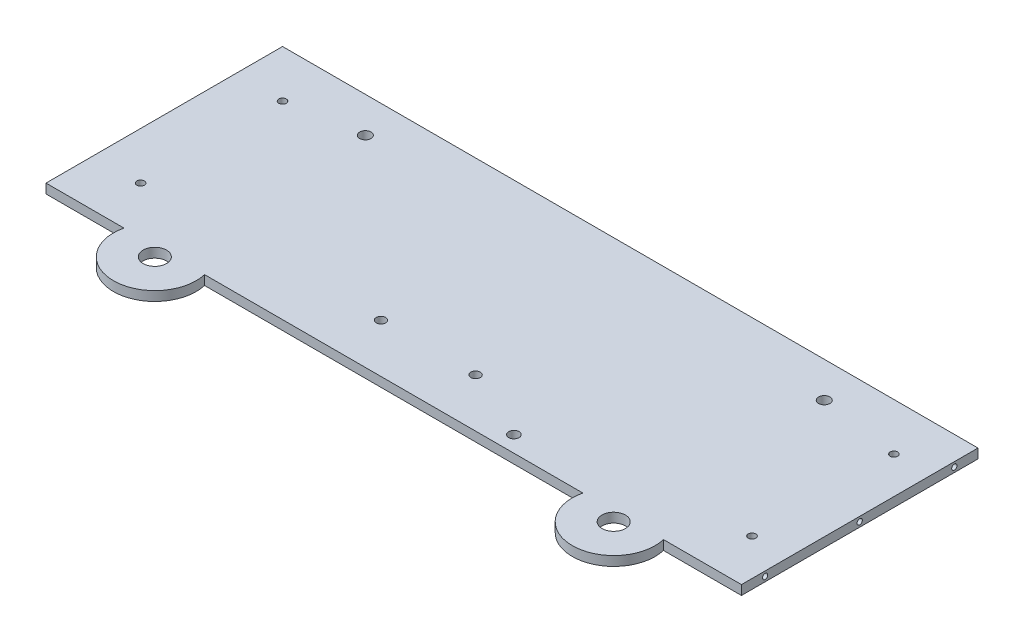
SolidWorks part; units mm, degrees
ref_plane "Front Plane" through (0, 0, 0) normal (0, 0, 1) x (1, 0, 0)
ref_plane "Top Plane" through (0, 0, 0) normal (0, 1, 0) x (1, 0, 0)
ref_plane "Right Plane" through (0, 0, 0) normal (1, 0, 0) x (0, 0, -1)
sketch "Sketch1" plane through (0, 0, 0) normal (0, 1, 0) x (1, 0, 0)
  line L0 (0, 0) -> (0, -63.5) construction
  line L1 (-186.69, -63.5) -> (186.69, -63.5)
  line L2 (-186.69, -63.5) -> (-186.69, 63.5)
  line L3 (-186.69, 63.5) -> (186.69, 63.5)
  line L4 (186.69, -63.5) -> (186.69, 63.5)
  line L5 (-186.69, -63.5) -> (186.69, 63.5) construction
  line L6 (-186.69, 63.5) -> (186.69, -63.5) construction
  line L7 (-123.19, -68.58) -> (-123.19, -63.5) construction
  line L8 (123.19, -68.58) -> (123.19, -63.5) construction
  line L9 (17.78, -37.338) -> (17.78, -63.5) construction
  circle A0 centre (-123.19, -68.58) radius 22.225
  circle A1 centre (123.19, -68.58) radius 22.225
  circle A2 centre (-123.19, -68.58) radius 6.2865
  circle A3 centre (123.19, -68.58) radius 6.2865
  circle A4 centre (-123.19, 44.45) radius 3.048
  circle A5 centre (123.19, 44.45) radius 3.048
  circle A6 centre (-33.02, -37.338) radius 2.54
  circle A7 centre (17.78, -37.338) radius 2.54
  circle A8 centre (0, -54.864) radius 3.175
  point P0 (0, 0)
  point P17 (123.19, 44.45)
  point P21 (-123.19, 44.45)
  dimension "D3" = 44.45
  dimension "D4" = 44.45
  dimension "D8" = 12.573
  dimension "D9" = 12.573
  dimension "D11" = 6.096
  dimension "D12" = 6.096
  dimension "D16" = 5.08
  dimension "D17" = 5.08
  dimension "D20" = 6.35
  dimension "D1" = 373.38
  dimension "D2" = 127
  dimension "D5" = 5.08
  dimension "D6" = 123.19
  dimension "D7" = 123.19
  dimension "D10" = 107.95
  dimension "D13" = 26.162
  dimension "D15" = 50.8
  dimension "D18" = 8.636
  dimension "D19" = 17.78
extrude "Boss-Extrude1" add sketch "Sketch1" along normal blind 5.0749 contours L1 A0 | L1 A1 | L3 L4 L1 L2 | A2 | A3 region at (-123.19, 0, 76.2008) region at (123.19, 0, 76.2008)
extrude "Cut-Extrude1" cut sketch "Sketch1<5>" along normal through all contours A3 | A2
sketch "Sketch1<5>" plane through (0, 0, 0) normal (0, 1, 0) x (1, 0, 0) same geometry as "Sketch1"
extrude "Cut-Extrude2" cut sketch "Sketch1<7>" along normal through all and the other way through all contours A4 | A5
sketch "Sketch1<7>" plane through (0, 0, 0) normal (0, 1, 0) x (1, 0, 0) same geometry as "Sketch1"
extrude "Cut-Extrude3" cut sketch "Sketch1<8>" along normal through all contours A7 | A6
sketch "Sketch1<8>" plane through (0, 0, 0) normal (0, 1, 0) x (1, 0, 0) same geometry as "Sketch1"
hole_wizard "#21 (0.159) Diameter Hole1" positions "Sketch3" profile "Sketch4" hole size "#21" standard "ANSI Inch" end condition through all
sketch "Sketch3" plane through (0, 5.0749, 0) normal (0, 1, 0) x (1, 0, 0)
  line L0 (-186.69, 63.5) -> (186.69, 63.5) construction
  line L1 (-186.69, -63.5) -> (-186.69, 63.5) construction
  line L2 (-186.69, -63.5) -> (-144.8266, -63.5) construction
  point P0 (-161.29, 38.1)
  point P2 (-161.29, -38.1)
  point P4 (166.9543, -38.1)
  point P6 (166.9543, 38.1)
  dimension "D1" = 25.4
  dimension "D2" = 25.4
  dimension "D3" = 25.4
  dimension "D4" = 25.4
sketch "Sketch4" plane through (-161.29, 5.0749, -38.1) normal (1, 0, 0) x (0, 0, 1)
  line L0 (0, 0) -> (0, 5.0749)
  line L1 (0, 5.0749) -> (2.0193, 5.0749)
  line L2 (2.0193, 5.0749) -> (2.0193, 0)
  line L5 (2.0193, 0) -> (0, 0)
  line L11 (0, -6.35) -> (0, 107.95) construction
  dimension "Thru Hole Dia." = 4.0386
  dimension "Thru Hole Depth" = 5.0749
sketch "Sketch5" plane through (0, 5.0749, 0) normal (0, 1, 0) x (1, 0, 0)
  line L0 (186.69, -63.5) -> (186.69, 63.5) construction
  line L1 (-101.5534, -63.5) -> (101.5534, -63.5) construction
  circle A0 centre (55.88, -54.864) radius 2.794
  dimension "D1" = 8.636
  dimension "D2" = 130.81
extrude "Cut-Extrude4" cut sketch "Sketch5" against normal blind 5.08
sketch "Sketch6" plane through (186.69, 0, 0) normal (1, 0, 0) x (0, 0, -1)
  line L0 (63.5, 2.5375) -> (-63.5, 2.5375) construction
  line L1 (63.5, 5.0749) -> (63.5, 0) construction
  line L2 (-63.5, 5.0749) -> (-63.5, 0) construction
  circle A0 centre (0, 2.5375) radius 1.4224
  circle A1 centre (-50.8, 2.5375) radius 1.4224
  circle A2 centre (50.8, 2.5375) radius 1.4224
  dimension "D1" = 50.8
  dimension "D2" = 50.8
extrude "Cut-Extrude5" cut sketch "Sketch6" against normal blind 12.7
sketch "Sketch7" plane through (-186.69, 0, 0) normal (-1, 0, 0) x (0, 0, 1)
  line L0 (-63.5, 2.5375) -> (63.5, 2.5375) construction
  line L1 (-63.5, 5.0749) -> (-63.5, 0) construction
  line L2 (63.5, 5.0749) -> (63.5, 0) construction
  circle A0 centre (-50.8, 2.5375) radius 1.4224
  circle A1 centre (0, 2.5375) radius 1.4224
  point P12 (-76.5928, 69.3406)
  dimension "D1" = 12.7
  dimension "D2" = 50.8
extrude "Cut-Extrude6" cut sketch "Sketch7" against normal blind 12.7
